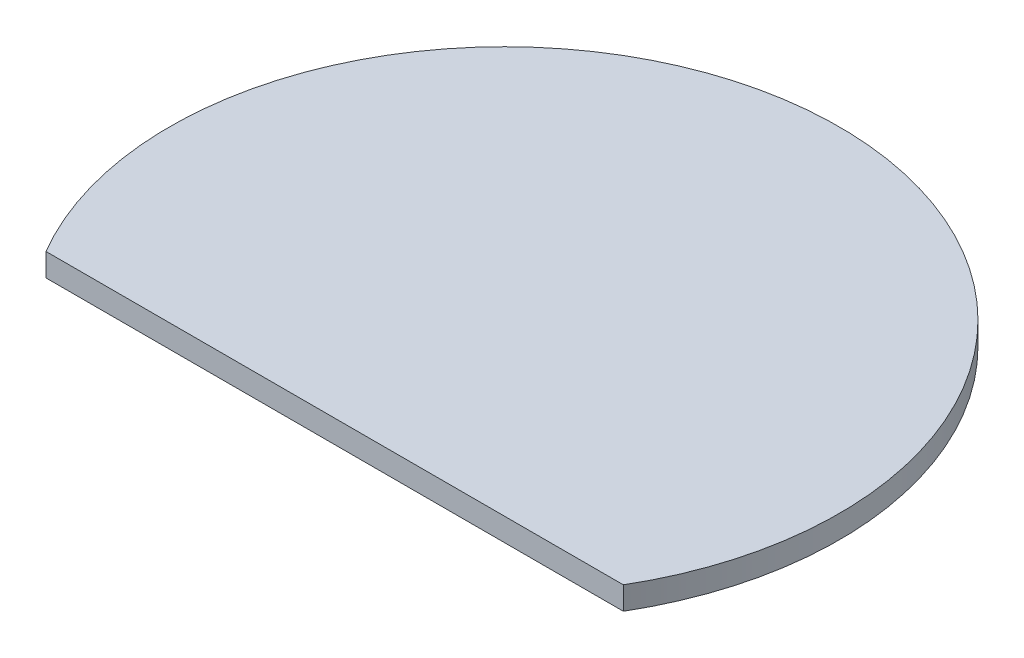
SolidWorks part; units mm, degrees
ref_plane "Front Plane" through (0, 0, 0) normal (0, 0, 1) x (1, 0, 0)
ref_plane "Top Plane" through (0, 0, 0) normal (0, 1, 0) x (1, 0, 0)
ref_plane "Right Plane" through (0, 0, 0) normal (1, 0, 0) x (0, 0, -1)
sketch "Sketch1" plane through (0, 0, 0) normal (0, 1, 0) x (1, 0, 0)
  line L0 (-12.5857, -7.4) -> (12.5857, -7.4)
  arc A0 (12.5857, -7.4) -> (-12.5857, -7.4) centre (0, 0) ccw
  dimension "D1" = 29.2
  dimension "D2" = 7.4
extrude "Boss-Extrude1" add sketch "Sketch1" along normal blind 1
